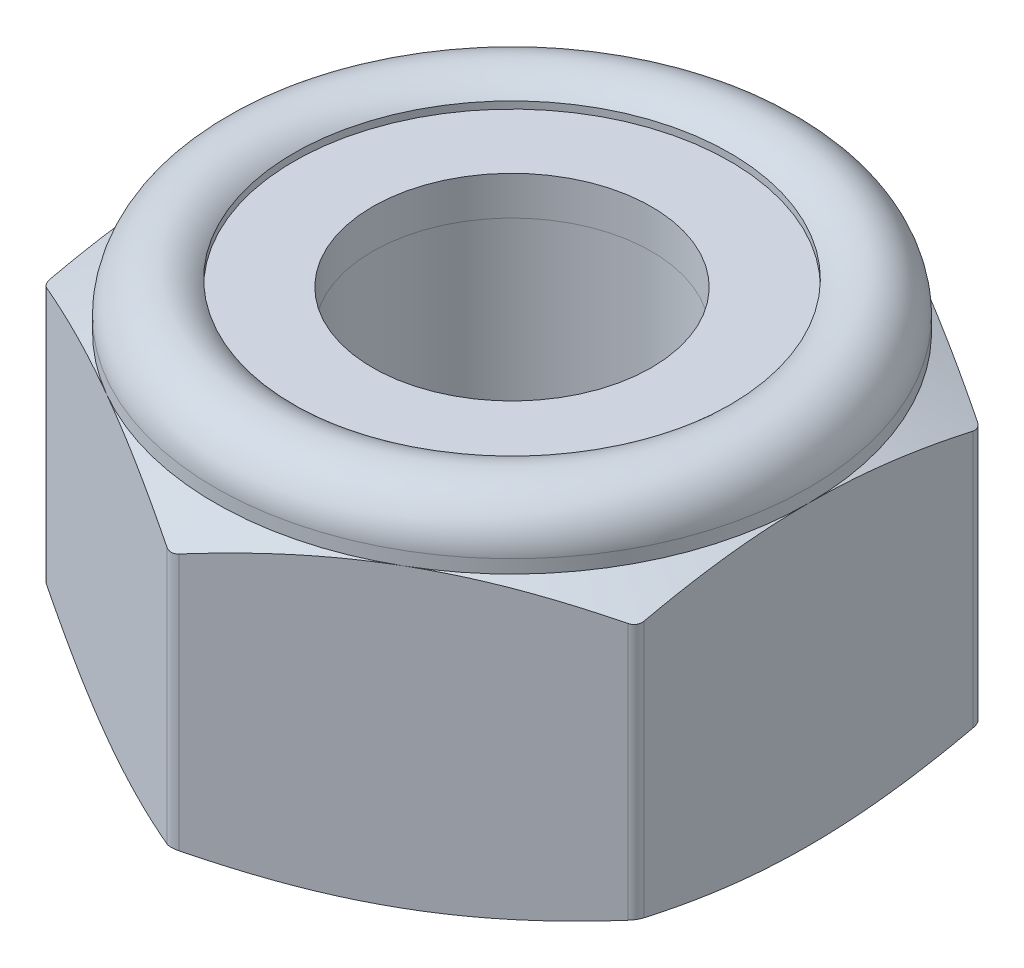
SolidWorks part; units mm, degrees
material "Alloy Steel"
ref_plane "Front Plane" through (0, 0, 0) normal (0, 0, 1) x (1, 0, 0)
ref_plane "Top Plane" through (0, 0, 0) normal (0, 1, 0) x (1, 0, 0)
ref_plane "Right Plane" through (0, 0, 0) normal (1, 0, 0) x (0, 0, -1)
sketch "Sketch1" plane through (0, 0, 0) normal (0, 0, 1) x (1, 0, 0)
  line L0 (0, -3) -> (0, 3) construction
  line L1 (5, 0) -> (-5, 0) construction
  line L2 (3, -3) -> (-3, -3) construction
  line L3 (3, -3) -> (3, -2) construction
  point P4 (0, 0)
  point P8 (0, 0)
  point P11 (0, -3)
  dimension "Height" = 6
  dimension "Width" = 10
  dimension "Thread Size" = 6
  dimension "Thread Pitch" = 1
sketch "Sketch2" plane through (0, 0, 0) normal (0, 1, 0) x (1, 0, 0)
  line L0 (-3, 0.4375) -> (-3, -0.4375) construction
  line L1 (0, 5.7735) -> (-5, 2.8868)
  line L2 (-5, 2.8868) -> (-5, -2.8868)
  line L3 (-5, -2.8868) -> (0, -5.7735)
  line L4 (0, -5.7735) -> (5, -2.8868)
  line L5 (5, -2.8868) -> (5, 2.8868)
  line L6 (5, 2.8868) -> (0, 5.7735)
  line L7 (-3, -0.4375) -> (-2.3505, -0.0625) construction
  line L8 (-2.3505, -0.0625) -> (-2.3505, 0.0625) construction
  line L9 (-2.3505, 0.0625) -> (-3, 0.4375) construction
  line L10 (-2.3505, 0) -> (-3, 0) construction
  line L11 (-2.6752, 0.25) -> (-2.6752, -0.25) construction
  line L12 (3, 0) -> (-3, 0) construction
  line L13 (5, 0) -> (-5, 0) construction
  circle A0 centre (0, 0) radius 5 construction
  circle A1 centre (0, 0) radius 2.3505
  point P19 (0, -2.3505)
  dimension "D1" = 0.125
  dimension "D2" = 0.5
  dimension "D3" = 60
extrude "Boss-Extrude1" add sketch "Sketch2" along normal up to vertex (3 mm away) and the other way up to vertex (3 mm away) up to point (0, 3, 0) other way up to point (0, -3, 0)
fillet "Fillet1" radius 0.2 6 edges at (-5, 0, -2.8868) (0, 0, -5.7735) (-5, 0, 2.8868) (5, 0, -2.8868) (5, 0, 2.8868) (0, 0, 5.7735)
sketch "Sketch3" plane through (0, 0, 0) normal (1, 0, 0) x (0, 0, -1)
  line L0 (5.7735, 2) -> (5.7735, 4)
  line L2 (5, -3) -> (5.7735, -2.6393)
  line L3 (2.9445, -3) -> (5.7158, -3) construction
  line L4 (5.7735, 3) -> (5.7735, -3) construction
  line L5 (5.7735, -2.6393) -> (5.7735, -3)
  line L6 (5.7735, -3) -> (5, -3)
  line L7 (5, 2) -> (5.7735, 1.6393)
  line L8 (5.7735, 1.6393) -> (5.7735, 2)
  line L11 (5, 2) -> (5, 2.224)
  line L12 (2.9445, 3) -> (5.7158, 3) construction
  line L13 (2.3505, 2) -> (3.6752, 2)
  line L14 (3.6752, 2) -> (3.6752, 2.7727)
  line L15 (3.6752, 2) -> (5, 2) construction
  line L16 (3.6752, 2.7727) -> (4.224, 2.224) construction
  line L17 (4.224, 2.224) -> (4.224, 3) construction
  line L18 (2.3505, 2) -> (2.3505, 4)
  line L19 (2.3505, 4) -> (5.7735, 4)
  line L21 (2.3505, -3) -> (2.3505, -2.4)
  line L22 (-2.7713, -3) -> (2.7713, -3) construction
  line L24 (2.9505, -3) -> (2.3505, -3)
  line L25 (2.3505, -2.4) -> (2.9505, -3)
  arc A0 (5, 2.224) -> (3.6752, 2.7727) centre (4.224, 2.224) ccw
  point P0 (5, 2)
  point P1 (5, 0)
  point P14 (2.3505, 0)
  dimension "D1" = 5
  dimension "D2" = 25
  dimension "D3" = 45
  dimension "D4" = 1
  dimension "D5" = 0.6
revolve "Cut-Revolve2" cut sketch "Sketch3" angle 360 about L0
sketch "Sketch4" plane through (0, 0, 0) normal (1, 0, 0) x (0, 0, -1)
  line L0 (-3.6752, 2.7727) -> (-3.6752, 2) construction
  line L1 (-2.3505, 2) -> (-3.6752, 2)
  line L2 (-2.3505, 2) -> (-2.3505, 2.6527)
  line L3 (-2.3505, 2.6527) -> (-3.6752, 2.6527)
  line L4 (-3.6752, 2) -> (-3.6752, 2.6527)
  line L5 (3.6752, 2.7727) -> (-3.6752, 2.7727) construction
  line L6 (2.3505, 2) -> (-2.3505, 2) construction
  dimension "D1" = 0.12
revolve "Revolve1" add sketch "Sketch4" angle 360 about L0
sketch "Sketch5" plane through (0, 0, 0) normal (0, 1, 0) x (1, 0, 0)
  circle A0 centre (0, 0) radius 2.3505 construction
  point P0 (0, -2.3505)
sketch "Sketch6" [suppressed] plane through (0, 0, 0) normal (0, 0, 1) x (1, 0, 0)
  line L0 (3, 2) -> (3, -3)
  line L2 (0, -3) -> (5, -3) construction
  line L3 (3, -3) -> (0, -3)
  line L4 (0, -3) -> (0, 2)
  line L5 (0, -3) -> (0, 3) construction
  line L6 (0, 2) -> (3, 2)
  line L7 (5, 2) -> (2.5, 2) construction
revolve "Revolve2" [suppressed] add sketch "Sketch6" angle 360 about L4
sketch "Sketch7" [suppressed] plane through (0, -3, 0) normal (0, -1, 0) x (1, 0, 0)
  circle A2 centre (0, 0) radius 3
  circle A3 centre (0, 0) radius 3
  dimension "D1" = 0
curve "Helix/Spiral1" [suppressed] pitch 1 height 6 turns 6
sketch "Sketch8" [suppressed] plane through (0, 0, 0) normal (0, 0, 1) x (1, 0, 0)
  line L0 (3.1083, -2.9375) -> (2.2422, -3.4375) construction
  line L1 (2.2422, -3.4375) -> (3.1083, -3.9375) construction
  line L2 (3.1083, -3.9375) -> (3.1083, -2.9375) construction
  line L3 (2.3505, -3.375) -> (2.3505, -3.5)
  line L4 (3, -3) -> (3, -3.875) construction
  line L5 (3, -3.4375) -> (3.1083, -3.4375) construction
  line L6 (2.2422, -3.4375) -> (2.3505, -3.4375) construction
  line L7 (3.0541, -3.4375) -> (3.0541, -3.9062) construction
  line L8 (2.3505, -3.375) -> (3.1083, -2.9375)
  line L9 (3.1083, -2.9375) -> (3.0541, -3.9062)
  line L10 (2.3505, -3.5) -> (3.0541, -3.9062)
  dimension "D1" = 1
  dimension "D2" = 0.125
sweep "Cut-Sweep1" [suppressed] cut profiles "Sketch8" path "Helix/Spiral1"
sketch "Sketch9" [suppressed] plane through (0, 0, 0) normal (0, 0, 1) x (1, 0, 0)
  line L0 (0, 0) -> (0, -3)
  line L1 (0, 0) -> (0, 0.6)
  line L2 (0, -3) -> (3, -3)
  line L3 (3, -3) -> (3.6, -3)
  line L4 (3.6, -3) -> (0, 0.6)
  dimension "D1" = 0.6
revolve "Revolve3" [suppressed] add sketch "Sketch9" angle 360 about L0
sketch "Sketch10" [suppressed] plane through (0, -3, 0) normal (0, -1, 0) x (1, 0, 0)
  circle A0 centre (0, 0) radius 2.9505 construction
  circle A1 centre (0, 0) radius 2.9505
extrude "Boss-Extrude2" [suppressed] add sketch "Sketch10" against normal up to surface (5 mm away)
combine bodies "Combine1" [suppressed] operation type subtract main body 110 bodies to subtract 109
equation "\"D1@Sketch3\"=\"Height@sketch1\"*(5/6)"
equation "\"D5@Sketch3\"=\"Thread Size@Sketch1\"*.1"
equation "\"D4@Helix/Spiral1\"=\"Thread Pitch@sketch1\""
equation "\"D3@Helix/Spiral1\"=\"Height@sketch1\""
equation "\"D1@Sketch8\"=\"Thread Pitch@sketch1\""
equation "\"D2@Sketch8\"=\"Thread Pitch@sketch1\"/8"
equation "\"D1@Sketch9\"=\"Thread Size@Sketch1\" * .1"
equation "\"D1@Sketch2\"=\"Thread Pitch@sketch1\"/8"
equation "\"D2@Sketch2\"=\"Thread Pitch@sketch1\"/2"
equation "\"D1@Sketch4\" = \"Height@Sketch1\" * .02"
equation "\"D1@Fillet1\"=\"Width@sketch1\"*.02"
